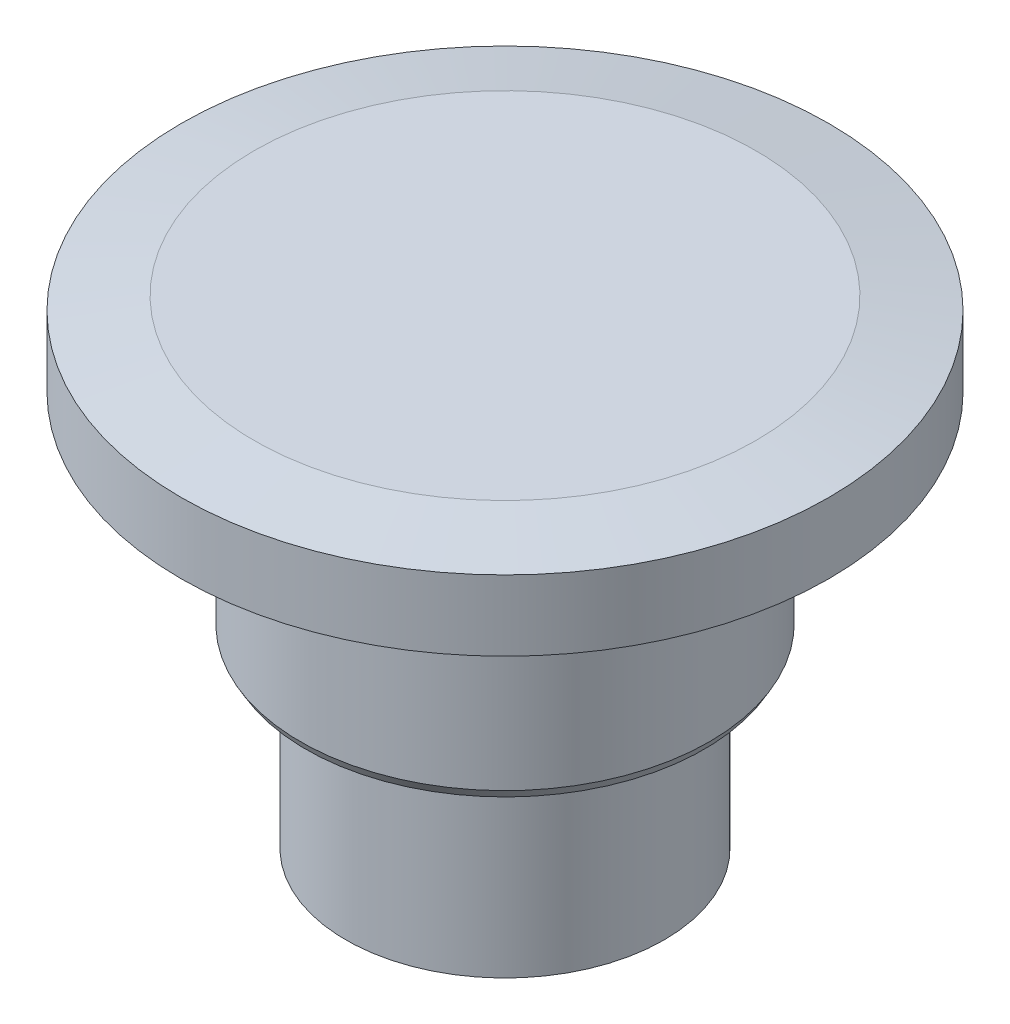
SolidWorks part; units mm, degrees
material "ABS"
ref_plane "Front Plane" through (0, 0, 0) normal (0, 0, 1) x (1, 0, 0)
ref_plane "Top Plane" through (0, 0, 0) normal (0, 1, 0) x (1, 0, 0)
ref_plane "Right Plane" through (0, 0, 0) normal (1, 0, 0) x (0, 0, -1)
sketch "Sketch1" plane through (0, 0, 0) normal (0, 0, 1) x (1, 0, 0)
  line L0 (-17.5, 4.8054) -> (-13.5608, 5.5)
  line L1 (-12.05, 0) -> (-17.5, 0)
  line L2 (0, -16.35) -> (0, 5.5)
  line L3 (0, 5.5) -> (-13.5608, 5.5)
  line L4 (-17.5, 0) -> (-17.5, 4.8054)
  line L12 (-11.05, -0.35) -> (-11.05, -10.35)
  line L13 (-11.05, -10.35) -> (-5.6, -10.35)
  line L15 (-12.05, 0) -> (-12.05, -0.35)
  line L16 (-12.05, -0.35) -> (-11.05, -0.35)
  line L20 (-3, -10.1) -> (-3, -16.35)
  line L21 (-3, -16.35) -> (0, -16.35)
  line L22 (-3, -10.1) -> (-5.6, -10.1)
  line L23 (-5.6, -10.35) -> (-5.6, -10.1)
  dimension "D5" = 5.5
  dimension "D6" = 4
  dimension "D7" = 10
  dimension "D4" = 17.5
  dimension "D9" = 0.35
  dimension "D8" = 10
  dimension "D11" = 3
  dimension "Bearing ID" = 11.05
  dimension "D2" = 5.6
  dimension "D3" = 0.25
revolve "Revolve1" add sketch "Sketch1" angle 360 about L2
chamfer "Chamfer2" distance 1 angle 83 1 edges at (17.5, 0, 0)
sketch "Sketch8" plane through (0, -10.35, 0) normal (0, -1, 0) x (1, 0, 0)
  circle A0 centre (0, 0) radius 5.6
  circle A1 centre (0, 0) radius 5.6 construction
  circle A2 centre (0, 0) radius 8.6
  dimension "D1" = 3
extrude "Boss-Extrude7" add sketch "Sketch8" along normal blind 10
sketch "Sketch2" plane through (0, -16.35, 0) normal (0, -1, 0) x (1, 0, 0)
  line L6 (-6.25, 1.85) -> (-7, 1.1)
  line L7 (-0.75, -1.85) -> (-6.25, -1.85)
  line L8 (0, -1.1) -> (0, 1.1)
  line L9 (-0.75, 1.85) -> (-6.25, 1.85)
  line L10 (-7, -1.1) -> (-7, 1.1)
  line L11 (0, -1.85) -> (-7, 1.85) construction
  line L12 (0, 1.85) -> (-7, -1.85) construction
  line L13 (-6.25, -1.85) -> (-7, -1.1)
  line L14 (0, -1.1) -> (-0.75, -1.85)
  line L15 (0, 1.1) -> (-0.75, 1.85)
  circle A0 centre (0, 0) radius 11.05 construction
  circle A1 centre (0, 0) radius 11.05 construction
  point P0 (-3.5, 0)
  point P4 (0, 0)
  point P15 (-11.05, 0)
  circle M4 centre (0, 0) radius 3
  dimension "D2" = 3.7
  dimension "D1" = 7
extrude "Cut-Extrude1" cut sketch "Sketch2" against normal up to surface and the other way up to surface contours L8 L15 L9 L7 L14 M4 | L13 L7 L9 L6 L10 M4 up to face at (5.6, -10.1, 0) other way up to face at (8.6, -20.35, 0)
sketch "Sketch5" plane through (0, 0, 0) normal (0, 1, 0) x (1, 0, 0)
  circle A0 centre (-17.5, 0) radius 0.125
  circle A1 centre (0, 0) radius 17.5 construction
  circle A2 centre (17.5, 0) radius 0.125
  circle A3 centre (0, 17.5) radius 0.125
  circle A4 centre (0, -17.5) radius 0.125
  dimension "D1" = 0.25
extrude "Cut-Extrude2" [suppressed] cut sketch "Sketch5" against normal through all both and the other way through all contours A0
chamfer "Chamfer1" distance 1 angle 45 1 edges at (5.6, -20.35, 0)
chamfer "Chamfer3" distance 0.5 angle 30 1 edges at (11.05, -10.35, 0)
equation "\"BearingID\"= 22.1"
equation "\"Bearing ID@Sketch1\"= \"BearingID\" / 2"
